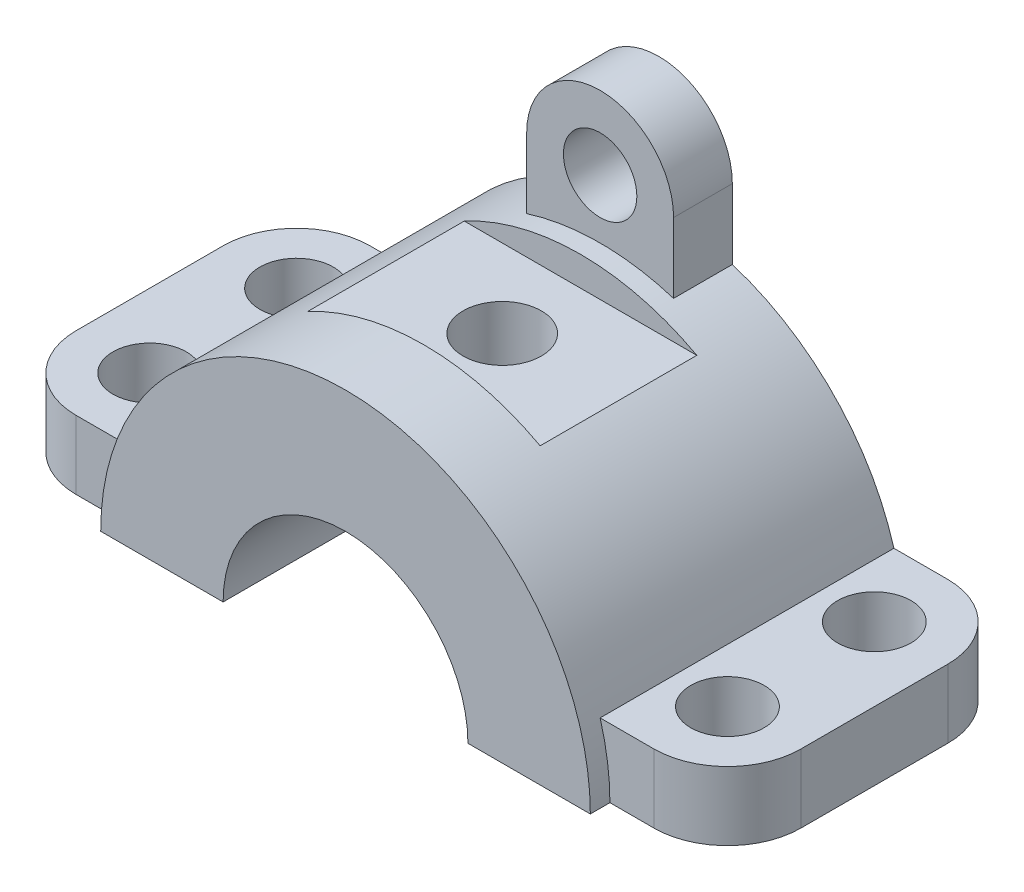
SolidWorks part; units mm, degrees
ref_plane "前视基准面" through (0, 0, 0) normal (0, 0, 1) x (1, 0, 0)
ref_plane "上视基准面" through (0, 0, 0) normal (0, 1, 0) x (1, 0, 0)
ref_plane "右视基准面" through (0, 0, 0) normal (1, 0, 0) x (0, 0, -1)
other "Configuration Table"
sketch "草图1" plane through (0, 0, 0) normal (0, 0, 1) x (1, 0, 0)
  line L0 (-988.7152, 0) -> (48447.0459, 0) construction
  line L1 (0, 0) -> (0, 106.9256) construction
  line L2 (-74, 0) -> (-50, 0)
  line L3 (-74, 0) -> (-74, 14)
  line L4 (-74, 14) -> (-48, 14)
  line L6 (74, 0) -> (50, 0)
  line L7 (74, 0) -> (74, 14)
  line L8 (74, 14) -> (48, 14)
  line L9 (-15, 62) -> (-15, 47.697)
  line L10 (15, 62) -> (15, 47.697)
  line L11 (-50, 0) -> (-25, 0)
  line L12 (25, 0) -> (50, 0)
  arc A0 (25, 0) -> (-25, 0) centre (0, 0) ccw
  arc A1 (50, 0) -> (-50, 0) centre (0, 0) ccw
  circle A2 centre (0, 62) radius 7.5
  arc A3 (15, 62) -> (-15, 62) centre (0, 62) ccw
  point P17 (-54.08, 0)
  point P24 (0, 0)
  dimension "D1" = 25
  dimension "D2" = 50
  dimension "D5" = 15
  dimension "D6" = 15
  dimension "D3" = 14
  dimension "D4" = 62
  dimension "D7" = 148
extrude "凸台-拉伸1" add sketch "草图1" along normal blind 64 contours L12 A1 L11 A0 region at (-48.3907, 6.913, 0)
extrude "凸台-拉伸2" add sketch "草图1<3>" along normal blind 60 contours A1 L4 L3 L2 | A1 L6 L7 L8 region at (-61.6622, 7.0942, 0) region at (61.6622, 7.0942, 0)
sketch "草图1<3>" plane through (0, 0, 0) normal (0, 0, 1) x (1, 0, 0) same geometry as "草图1"
extrude "凸台-拉伸3" add sketch "草图1<4>" along normal blind 12 contours L10 A3 L9 A1 A2 region at (-14.5806, 54.8485, 0)
sketch "草图1<4>" plane through (0, 0, 0) normal (0, 0, 1) x (1, 0, 0) same geometry as "草图1"
fillet "圆角1" radius 15 4 edges at (74, 7, 0) (74, 7, 60) (-74, 7, 60) (-74, 7, 0)
sketch "草图3" plane through (0, 14, 0) normal (0, 1, 0) x (1, 0, 0)
  line L16 (-926, -30) -> (49074, -30) construction
  line L17 (74, -45) -> (74, -15) construction
  line L18 (0, -1000.5508) -> (0, 48999.4492) construction
  arc A3 (-59, 0) -> (-74, -15) centre (-59, -15) ccw construction
  arc A7 (-59, 0) -> (-74, -15) centre (-59, -15) ccw construction
  circle A8 centre (-59, -15) radius 7.5
  circle A9 centre (-59, -45) radius 7.5
  circle A10 centre (59, -15) radius 7.5
  circle A11 centre (59, -45) radius 7.5
  point P6 (74, -30)
  dimension "D1" = 15
extrude "切除-拉伸1" cut sketch "草图3" against normal through all both and the other way through all
sketch "草图4" plane through (0, 0, 64) normal (0, 0, 1) x (1, 0, 0)
  line L0 (-23.7487, 44) -> (23.7487, 44)
  arc A0 (50, 0) -> (-50, 0) centre (0, 0) ccw construction
  arc A1 (23.7487, 44) -> (-23.7487, 44) centre (0, 0) ccw
  point P5 (0, 50)
  dimension "D1" = 6
extrude "切除-拉伸2" cut sketch "草图4" against normal blind 32 from offset 16 offset against normal yes
sketch "草图5" plane through (0, 44, 0) normal (0, 1, 0) x (1, 0, 0)
  line L0 (-23.7487, -16) -> (23.7487, -48) construction
  line L4 (-23.7487, -48) -> (23.7487, -48)
  line L5 (23.7487, -48) -> (23.7487, -16)
  line L6 (23.7487, -16) -> (-23.7487, -16)
  line L7 (-23.7487, -16) -> (-23.7487, -48)
  line L8 (-23.7487, -48) -> (23.7487, -48) construction
  line L9 (23.7487, -48) -> (23.7487, -16) construction
  line L10 (23.7487, -16) -> (-23.7487, -16) construction
  line L11 (-23.7487, -16) -> (-23.7487, -48) construction
  circle A0 centre (0, -32) radius 8
  dimension "D2" = 16
  dimension "D1" = 0
extrude "切除-拉伸3" cut sketch "草图5" against normal through all
